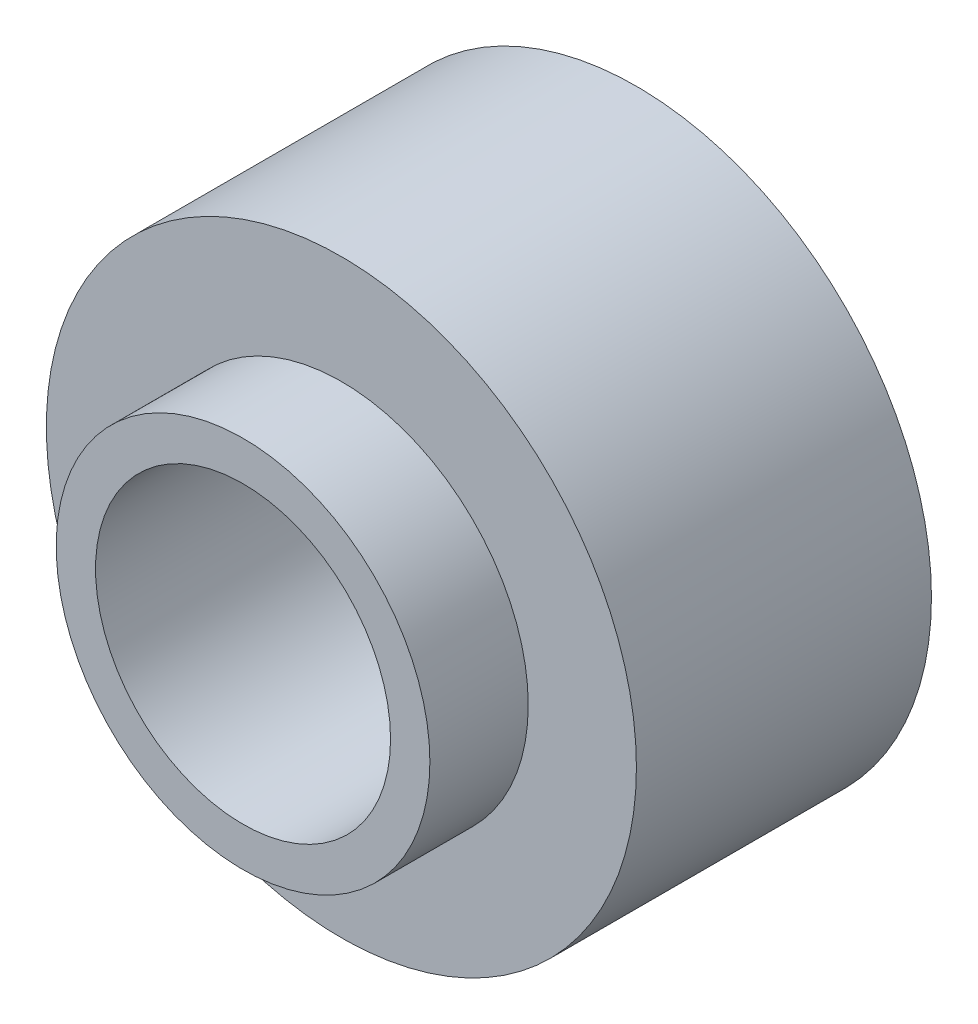
SolidWorks part; units mm, degrees
material "Plain Carbon Steel"
ref_plane "Front Plane" through (0, 0, 0) normal (0, 0, 1) x (1, 0, 0)
ref_plane "Top Plane" through (0, 0, 0) normal (0, 1, 0) x (1, 0, 0)
ref_plane "Right Plane" through (0, 0, 0) normal (1, 0, 0) x (0, 0, -1)
sketch "Sketch1" plane through (0, 0, 0) normal (0, 0, 1) x (1, 0, 0)
  circle A0 centre (0, 0) radius 9.525
  circle A1 centre (0, 0) radius 6.0325
  circle A2 centre (0, 0) radius 4.7625
  dimension "D1" = 19.05
  dimension "D2" = 1.27
  dimension "D3" = 9.525
extrude "Boss-Extrude1" add sketch "Sketch1" against normal blind 9.525 contours A0 A1 | A1 A2 region at (-9.2556, 0, 0) region at (-5.8619, 0, 0)
extrude "Boss-Extrude2" add sketch "Sketch1<4>" along normal blind 3.175 contours A1 A2 region at (-5.8619, 0, 0)
sketch "Sketch1<4>" plane through (0, 0, 0) normal (0, 0, 1) x (1, 0, 0) same geometry as "Sketch1"
